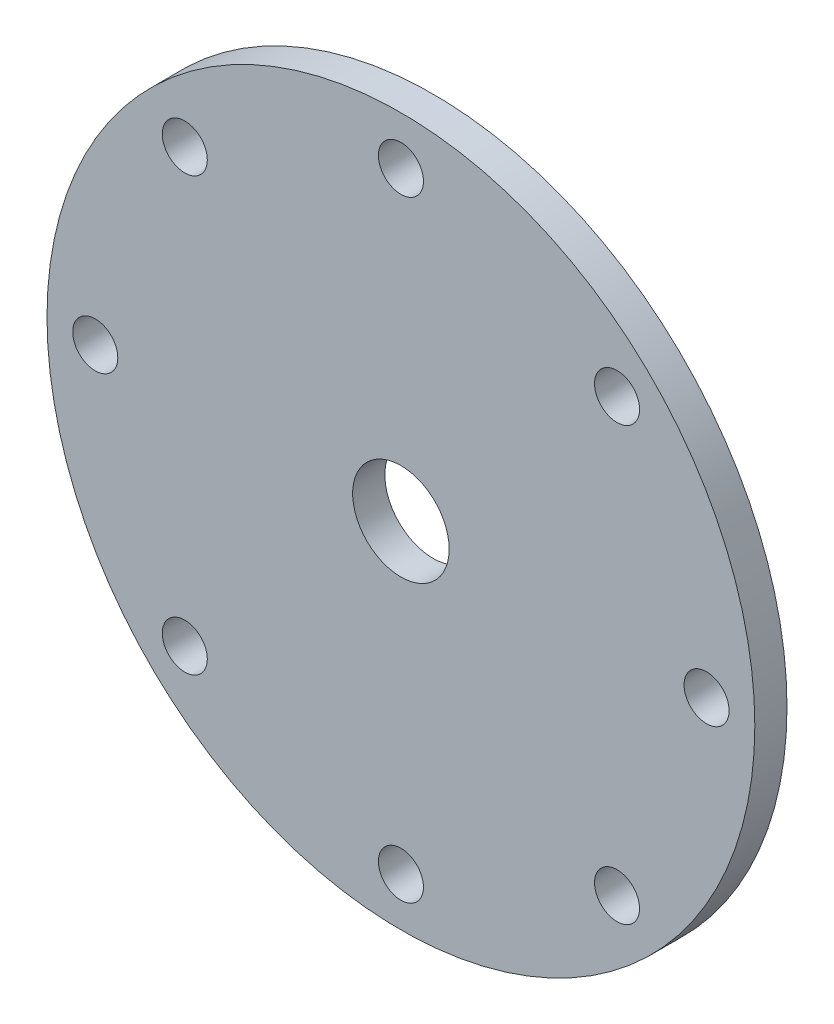
SolidWorks part; units mm, degrees
ref_plane "Front Plane" through (0, 0, 0) normal (0, 0, 1) x (1, 0, 0)
ref_plane "Top Plane" through (0, 0, 0) normal (0, 1, 0) x (1, 0, 0)
ref_plane "Right Plane" through (0, 0, 0) normal (1, 0, 0) x (0, 0, -1)
sketch "Sketch1" plane through (0, 0, 0) normal (0, 0, 1) x (1, 0, 0)
  line L0 (0, 55) -> (0, -55) construction
  line L1 (-55, 0) -> (55, 0) construction
  line L2 (-33.5876, 33.5876) -> (33.5876, -33.5876) construction
  line L3 (-33.5876, -33.5876) -> (33.5876, 33.5876) construction
  circle A0 centre (0, 0) radius 55
  circle A1 centre (0, 0) radius 7.5
  circle A2 centre (0, 47.5) radius 3.5
  circle A6 centre (33.5876, 33.5876) radius 3.5
  circle A7 centre (47.5, 0) radius 3.5
  circle A8 centre (33.5876, -33.5876) radius 3.5
  circle A9 centre (0, -47.5) radius 3.5
  circle A10 centre (-33.5876, -33.5876) radius 3.5
  circle A11 centre (-47.5, 0) radius 3.5
  circle A12 centre (-33.5876, 33.5876) radius 3.5
  point P8 (-30.0743, -25.1058)
  point P9 (0, 47.5)
  point P26 (0, 0)
  point P27 (0, 0)
  point P28 (0, -33.5876)
  point P29 (0, -31.2637)
  point P30 (0, 47.5)
  point P31 (0, -33.3795)
  dimension "D1" = 110
  dimension "D2" = 15
  dimension "D3" = 7
  dimension "D6" = 47.5
  dimension "D4" = 47.5
  dimension "D5" = 8
extrude "Rotor Disc" add sketch "Sketch1" along normal blind 5 contours A0 A12 A11 A10 A8 A7 A6 A1 A2 region at (-53.4444, 0, 0)
